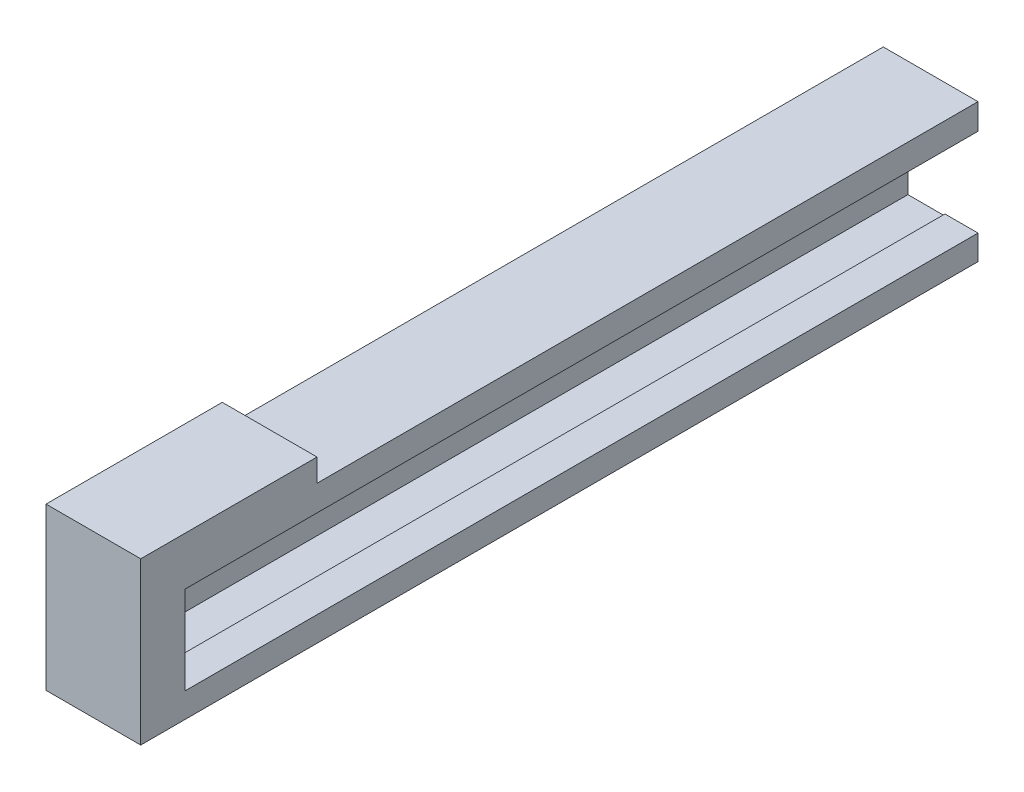
SolidWorks part; units mm, degrees
ref_plane "Front Plane" through (0, 0, 0) normal (0, 0, 1) x (1, 0, 0)
ref_plane "Top Plane" through (0, 0, 0) normal (0, 1, 0) x (1, 0, 0)
ref_plane "Right Plane" through (0, 0, 0) normal (1, 0, 0) x (0, 0, -1)
sketch "Sketch2" plane through (0, 0, 0) normal (0, 0, 1) x (1, 0, 0)
  line L0 (16.75, 6) -> (13, 6) construction
  line L1 (9, 6) -> (13, 6) construction
  line L2 (9, 8.5) -> (9, 6) construction
  line L3 (5, 8.5) -> (9, 8.5) construction
  line L4 (5, 13.5) -> (9, 13.5) construction
  line L5 (9, 16) -> (9, 13.5) construction
  line L6 (9, 16) -> (13, 16) construction
  line L7 (16.75, 16) -> (13, 16) construction
  line L8 (16.75, 6) -> (13, 6)
  line L9 (9, 6) -> (13, 6)
  line L10 (9, 8.5) -> (9, 6)
  line L11 (5, 8.5) -> (9, 8.5)
  line L12 (5, 13.5) -> (9, 13.5)
  line L13 (9, 16) -> (9, 13.5)
  line L14 (9, 16) -> (13, 16)
  line L15 (16.75, 16) -> (13, 16)
  line L16 (16.75, 26) -> (13, 26)
  line L17 (-1, 26) -> (13, 26)
  line L18 (-1, 26) -> (-1, 21.5)
  line L19 (-1, 21.5) -> (-1, 21.5)
  line L20 (5, 13.8) -> (8.7, 13.8)
  line L21 (8.7, 16.3) -> (8.7, 13.8)
  line L22 (8.7, 16.3) -> (13, 16.3)
  line L23 (16.75, 16.3) -> (13, 16.3)
  line L24 (5, 8.3) -> (8.8, 8.3)
  line L25 (8.8, 8.3) -> (8.8, 5.8)
  line L26 (8.8, 5.8) -> (13, 5.8)
  line L27 (16.75, 5.8) -> (13, 5.8)
  line L28 (13, 16.3) -> (13, 16)
  line L29 (13, 5.8) -> (13, 6)
  line L30 (16.75, 5.8) -> (16.75, 6)
  line L31 (16.75, 16.3) -> (16.75, 16)
  line L32 (6, 13.5) -> (6, 13.8)
  line L33 (6, 8.5) -> (6, 8.3)
  line L34 (5, 20) -> (5, 13.5) construction
  line L36 (16.75, 16.3) -> (8.7, 16.3)
  line L37 (16.75, 16.3) -> (16.75, 18.9132)
  line L38 (16.75, 18.9132) -> (8.7, 18.9132)
  line L39 (8.7, 16.3) -> (8.7, 18.9132)
  line L40 (8.7, 18.9132) -> (6, 18.9132)
  line L41 (8.7, 18.9132) -> (8.7, 13.8)
  line L42 (8.7, 13.8) -> (6, 13.8)
  line L43 (6, 18.9132) -> (6, 13.8)
  line L44 (16.75, 5.8) -> (8.8, 5.8)
  line L45 (16.75, 5.8) -> (16.75, 3.1868)
  line L46 (16.75, 3.1868) -> (8.8, 3.1868)
  line L47 (8.8, 5.8) -> (8.8, 3.1868)
  line L48 (8.8, 3.1868) -> (6, 3.1868)
  line L49 (8.8, 3.1868) -> (8.8, 8.3)
  line L50 (8.8, 8.3) -> (6, 8.3)
  line L51 (6, 3.1868) -> (6, 8.3)
  dimension "D4" = 1
  dimension "D1" = 10
  dimension "D2" = 0.3
  dimension "D3" = 0.2
extrude "Boss-Extrude3" add sketch "Sketch2" along normal blind 90 contours L31 L23 L28 L15 | L39 L22 L23 L37 L38 | L40 L43 L20 L21 L39 | L51 L48 L47 L25 L24 | L26 L47 L46 L45 L27 | L27 L30 L8 L29 region at (14.875, 5.9, 0) region at (12.775, 4.4934, 0) region at (7.4, 5.7434, 0) region at (7.35, 16.3566, 0) region at (14.875, 16.15, 0) region at (12.725, 17.6066, 0)
sketch "Sketch3" plane through (0, 0, 90) normal (0, 0, 1) x (1, 0, 0)
  line L0 (6, 8.3) -> (6, 3.1868) construction
  line L1 (6, 3.1868) -> (16.75, 3.1868) construction
  line L2 (16.75, 3.1868) -> (16.75, 6) construction
  line L3 (16.75, 6) -> (13, 6) construction
  line L4 (13, 6) -> (13, 5.8) construction
  line L5 (13, 5.8) -> (8.8, 5.8) construction
  line L6 (8.8, 5.8) -> (8.8, 8.3) construction
  line L7 (8.8, 8.3) -> (6, 8.3) construction
  line L8 (16.75, 16) -> (16.75, 18.9132)
  line L9 (16.75, 18.9132) -> (6, 18.9132)
  line L10 (6, 18.9132) -> (6, 13.8)
  line L11 (6, 13.8) -> (8.7, 13.8)
  line L12 (8.7, 13.8) -> (8.7, 16.3)
  line L13 (8.7, 16.3) -> (13, 16.3)
  line L14 (13, 16.3) -> (13, 16)
  line L15 (13, 16) -> (16.75, 16)
  line L16 (16.75, 16) -> (16.75, 18.9132)
  line L17 (16.75, 18.9132) -> (6, 18.9132)
  line L18 (6, 18.9132) -> (6, 13.8)
  line L19 (6, 13.8) -> (8.7, 13.8)
  line L20 (8.7, 13.8) -> (8.7, 16.3)
  line L21 (8.7, 16.3) -> (13, 16.3)
  line L22 (13, 16.3) -> (13, 16)
  line L23 (13, 16) -> (16.75, 16)
  line L24 (18.5681, 6) -> (18.5681, 16) construction
  line L25 (18.5681, 16) -> (13, 16) construction
  line L26 (13, 16) -> (13, 6) construction
  line L27 (13, 6) -> (18.5681, 6) construction
  line L28 (18.5681, 6) -> (18.5681, 16)
  line L29 (18.5681, 16) -> (13, 16)
  line L30 (13, 16) -> (13, 6)
  line L31 (13, 6) -> (18.5681, 6)
  line L32 (6, 8.3) -> (6, 3.1868)
  line L33 (6, 3.1868) -> (16.75, 3.1868)
  line L34 (16.75, 3.1868) -> (16.75, 6)
  line L35 (16.75, 6) -> (13, 6)
  line L36 (13, 6) -> (13, 5.8)
  line L37 (13, 5.8) -> (8.8, 5.8)
  line L38 (8.8, 5.8) -> (8.8, 8.3)
  line L39 (8.8, 8.3) -> (6, 8.3)
  line L40 (6, 13.8) -> (6, 8.3)
  line L41 (16.75, 16) -> (16.75, 6)
  line M42 (16.75, 16) -> (16.75, 18.9132)
  line M43 (16.75, 18.9132) -> (6, 18.9132)
  line M44 (6, 18.9132) -> (6, 13.8)
  line M45 (6, 13.8) -> (8.7, 13.8)
  line M46 (8.7, 13.8) -> (8.7, 16.3)
  line M47 (8.7, 16.3) -> (13, 16.3)
  line M48 (13, 16.3) -> (13, 16)
  line M49 (13, 16) -> (16.75, 16)
  dimension "D1" = 0
extrude "Boss-Extrude4" add sketch "Sketch3" along normal blind 5 contours L40 L39 L38 L37 L36 L30 M45 M48 M47 M46 | L30 L31 L28 L29 M49 | M49 M42 M43 M44 M45 M46 M47 M48 | L38 L39 L32 L33 L34 L31 L36 L37 region at (10.7291, 17.0813, 90) region at (14.875, 11, 90) region at (9.9889, 11.0667, 90) region at (10.6719, 5.0221, 90)
sketch "Sketch4" plane through (0, 0, 95) normal (0, 0, 1) x (1, 0, 0)
  line L0 (16.75, 3.1868) -> (16.75, 18.9132) construction
  line L1 (6, 18.9132) -> (16.75, 18.9132)
  line L2 (6, 18.9132) -> (6, 21.4917)
  line L3 (6, 21.4917) -> (16.75, 21.4917)
  line L4 (16.75, 18.9132) -> (16.75, 21.4917)
extrude "Boss-Extrude5" add sketch "Sketch4" against normal blind 20
sketch "Sketch5" plane through (0, 0, 95) normal (0, 0, 1) x (1, 0, 0)
  line L1 (16.75, 21.4917) -> (-3.25, 21.4917)
  line L2 (16.75, 21.4917) -> (16.75, 26.4917)
  line L3 (16.75, 26.4917) -> (-3.25, 26.4917)
  line L4 (-3.25, 21.4917) -> (-3.25, 26.4917)
  dimension "D1" = 20
  dimension "D2" = 5
extrude "Boss-Extrude6" [suppressed] add sketch "Sketch5" against normal blind 2
